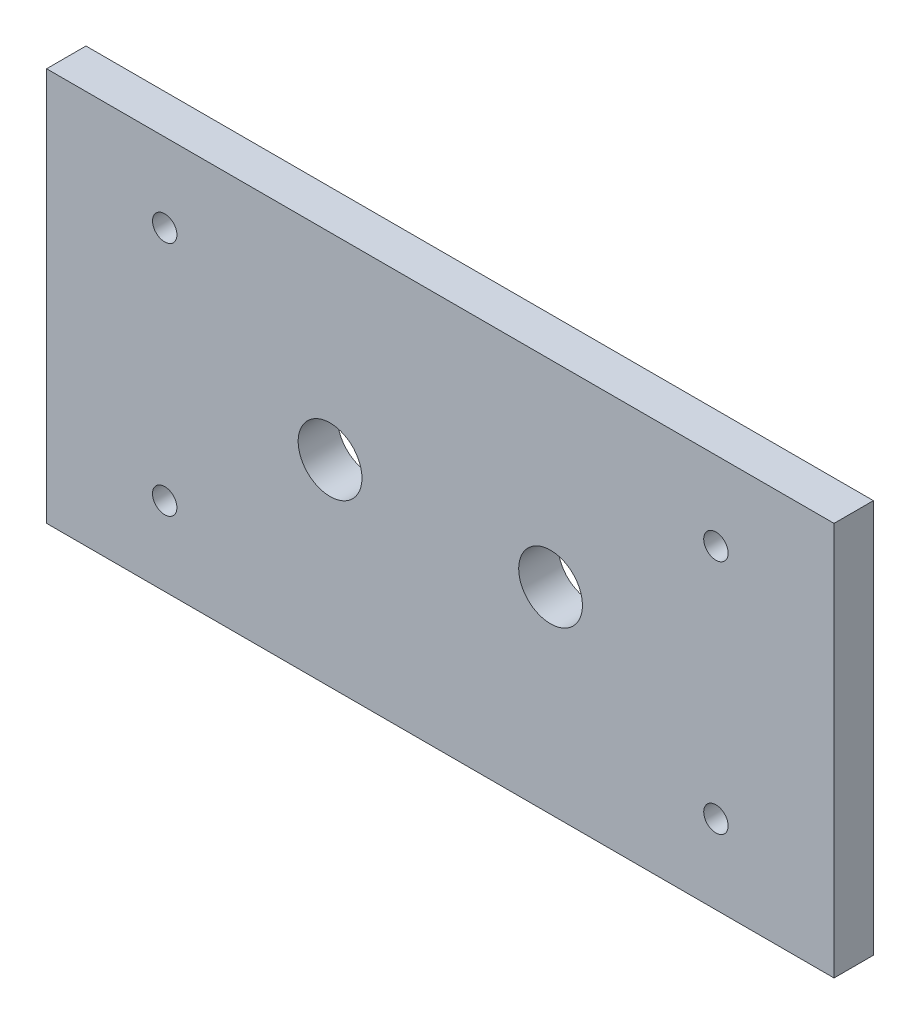
SolidWorks part; units mm, degrees
ref_plane "Plan de face" through (0, 0, 0) normal (0, 0, 1) x (1, 0, 0)
ref_plane "Plan de dessus" through (0, 0, 0) normal (0, 1, 0) x (1, 0, 0)
ref_plane "Plan de droite" through (0, 0, 0) normal (1, 0, 0) x (0, 0, -1)
sketch "Esquisse1" plane through (0, 0, 0) normal (0, 0, 1) x (1, 0, 0)
  line L0 (0, 0) -> (0, 16.8216) construction
  line L1 (-50, -25) -> (50, -25)
  line L2 (-50, -25) -> (-50, 25)
  line L3 (-50, 25) -> (50, 25)
  line L4 (50, -25) -> (50, 25)
  line L5 (-50, -25) -> (50, 25) construction
  line L6 (-50, 25) -> (50, -25) construction
  line L7 (0, 0) -> (42.1574, 0) construction
  circle A0 centre (-35, -15) radius 1.55
  circle A1 centre (-35, 15) radius 1.55
  circle A2 centre (35, -15) radius 1.55
  circle A3 centre (35, 15) radius 1.55
  circle A5 centre (-14, 0) radius 4.05
  circle A6 centre (14, 0) radius 4.05
  point P0 (0, 0)
  dimension "D3" = 3.1
  dimension "D7" = 8.1
  dimension "D1" = 100
  dimension "D2" = 50
  dimension "D4" = 15
  dimension "D5" = 10
  dimension "D9" = 14
  dimension "D10" = 25
extrude "Boss.-Extru.1" add sketch "Esquisse1" against normal blind 5
